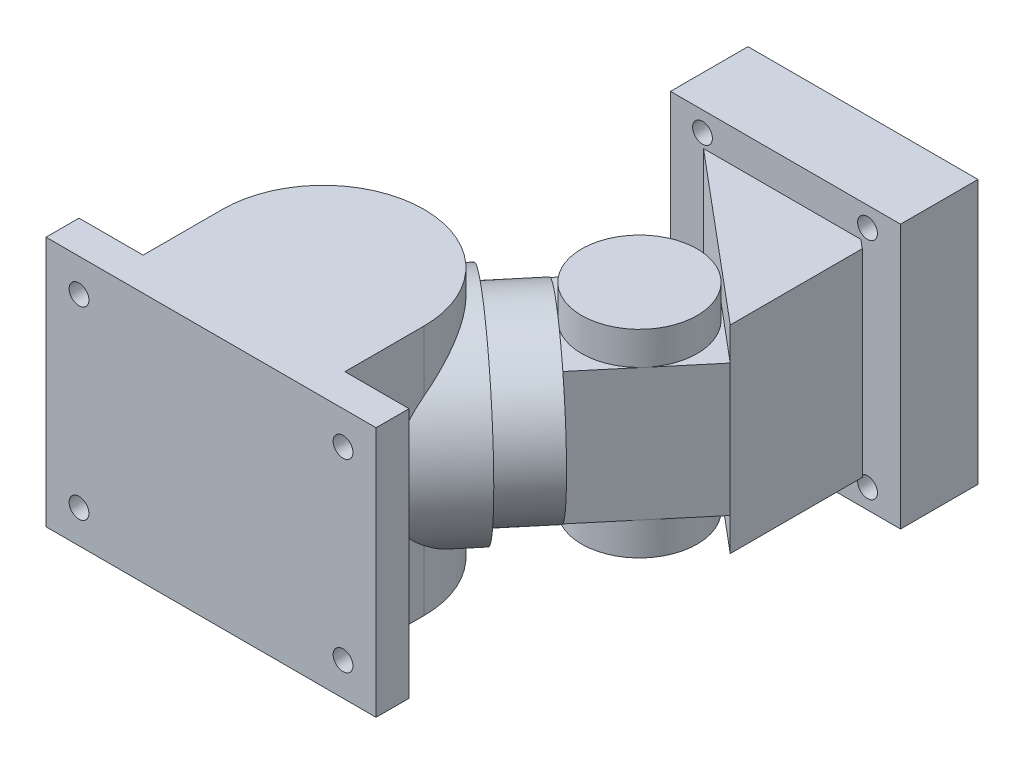
SolidWorks part; units mm, degrees
material "ABS"
ref_plane "Alzado" through (0, 0, 0) normal (0, 0, 1) x (1, 0, 0)
ref_plane "Planta" through (0, 0, 0) normal (0, 1, 0) x (1, 0, 0)
ref_plane "Vista lateral" through (0, 0, 0) normal (1, 0, 0) x (0, 0, -1)
sketch "Croquis1" plane through (0, 0, 0) normal (0, 1, 0) x (1, 0, 0)
  line L0 (0, 0) -> (0, 20)
  line L1 (0, 20) -> (-15.3209, 32.8558)
  line L2 (-15.3209, 32.8558) -> (-25.169, 21.1193)
  line L6 (0, 0) -> (-25.169, 21.1193)
  line L7 (0, 0) -> (-17.1631, 0) construction
  dimension "D1" = 20
  dimension "D2" = 20
  dimension "D5" = 130
extrude "Saliente-Extruir1" add sketch "Croquis1" along normal blind 15 and the other way blind 15
sketch "Croquis2" plane through (0, 0, 0) normal (0, 1, 0) x (1, 0, 0)
  line L0 (-13.4058, 11.2488) -> (0, 0)
  line L1 (-25.169, 21.1193) -> (0, 0) construction
  line L2 (0, 0) -> (-5.7851, -6.8944)
  line L4 (-19.1909, 4.3544) -> (-13.4058, 11.2488)
  circle A0 centre (-12.488, -1.27) radius 8.75
  point P4 (0, 0)
  point P5 (0, 0)
  point P10 (-26.0388, -3.8066)
  dimension "D1" = 17.5
  dimension "D2" = 90
  dimension "D3" = 90
  dimension "D4" = 9
extrude "Saliente-Extruir3" add sketch "Croquis2" along normal blind 10 and the other way blind 10 contours A0 | A0 L0 L4 | A0 L2 L0 region at (-6.7199, 0, -5.6042) region at (-12.488, 0, 1.27)
sketch "Croquis4" plane through (0, 10, 0) normal (0, 1, 0) x (1, 0, 0)
  circle A0 centre (-12.488, -1.27) radius 8.75
  arc A1 (-19.1909, 4.3544) -> (-5.7851, -6.8944) centre (-12.488, -1.27) ccw construction
extrude "Saliente-Extruir9" add sketch "Croquis4" along normal blind 5 and the other way blind 25
sketch "Croquis5" plane through (0, 0, 0) normal (0, 1, 0) x (1, 0, 0)
  line L0 (-93.3589, -57.8135) -> (-14.6565, -57.8135)
  line L2 (-19.1909, 4.3544) -> (-24.976, -2.54)
  line L3 (-24.976, -2.54) -> (-11.5702, -13.7888)
  line L4 (-5.7851, -6.8944) -> (-11.5702, -13.7888)
  circle A0 centre (-12.488, -1.27) radius 8.75
  circle A1 centre (-12.488, -1.27) radius 8.75 construction
  point P5 (-12.8716, -31.2066)
  point P6 (0, 0)
  point P7 (0, 0)
  point P12 (-24.976, -37.1418)
  point P13 (-11.9019, -23.9717)
  dimension "D1" = 9
  dimension "D2" = 90
  dimension "D4" = 50
extrude "Saliente-Extruir10" add sketch "Croquis5" along normal blind 10 and the other way blind 10 contours A0 | A0 L2 L3 L4 region at (-18.1293, 0, 7.9931) region at (-12.488, 0, 1.27)
sketch "Croquis6" plane through (-11.5702, 0, 13.7888) normal (-0.6428, 0, 0.766) x (0.766, 0, 0.6428)
  line L0 (0, -10) -> (0, 10) construction
  circle A0 centre (-8.75, 0) radius 13.2877
  point P2 (-24.1554, -1.349)
  point P3 (0, 0)
  point P10 (0, 0)
extrude "Saliente-Extruir11" add sketch "Croquis6" along normal blind 8
sketch "Croquis7" plane through (-16.7125, 0, 19.9172) normal (-0.6428, 0, 0.766) x (0.766, 0, 0.6428)
  circle A0 centre (-8.75, 0) radius 15.2877
  circle A1 centre (-8.75, 0) radius 13.2877 construction
  dimension "D1" = 2
extrude "Saliente-Extruir12" add sketch "Croquis7" along normal blind 17
sketch "Croquis9" plane through (0, 0, 0) normal (0, 1, 0) x (1, 0, 0)
  line L2 (-46.0538, -17.4888) -> (-22.6317, -37.1423) construction
  circle A0 centre (-34.3428, -27.3155) radius 15.2877
extrude "Saliente-Extruir13" add sketch "Croquis9" along normal blind 17 and the other way blind 17 contours A0 | A0 region at (-34.3428, 0, 27.3155)
sketch "Croquis10" plane through (0, 17, 0) normal (0, 1, 0) x (1, 0, 0)
  line L0 (-49.6304, -27.3155) -> (-49.6304, -39.3155)
  line L1 (-49.6304, -39.3155) -> (-59.3428, -39.3155)
  line L2 (-59.3428, -39.3155) -> (-59.3428, -44.3155)
  line L3 (-59.3428, -44.3155) -> (-9.3428, -44.3155)
  line L4 (-9.3428, -44.3155) -> (-9.3428, -39.3155)
  line L5 (-9.3428, -39.3155) -> (-19.0551, -39.3155)
  line L6 (-19.0551, -27.3155) -> (-19.0551, -39.3155)
  arc A0 (-19.0551, -27.3155) -> (-49.6304, -27.3155) centre (-34.3428, -27.3155) ccw
  arc A2 (-22.6317, -37.1423) -> (-46.0538, -17.4888) centre (-34.3428, -27.3155) ccw construction
  point P1 (-88.8925, -113.8582)
  point P8 (0, 0)
  point P10 (-36.2233, -128.8582)
  point P13 (-31.3925, -128.8582)
  point P14 (-88.8925, -117.1694)
  point P18 (-56.5011, -66.6791)
  point P19 (0, 0)
  dimension "D3" = 25
  dimension "D1" = 5
  dimension "D2" = 50
  dimension "D5" = 12
extrude "Saliente-Extruir14" add sketch "Croquis10" along normal blind 2 and the other way blind 36
sketch "Croquis11" plane through (0, 15, 0) normal (0, 1, 0) x (1, 0, 0)
  line L0 (-30.169, 21.1193) -> (4.6791, 21.1193)
  line L1 (4.6791, 21.1193) -> (4.6791, 32.8558)
  line L2 (4.6791, 32.8558) -> (-30.169, 32.8558)
  line L3 (-30.169, 32.8558) -> (-30.169, 21.1193)
  point P5 (-32.8294, 39.3878)
  point P6 (-49.4345, 27.6398)
  point P7 (0, 0)
  point P9 (-2.6686, 29.1809)
  point P12 (4.6791, 21.1193)
  point P13 (0, 0)
  point P14 (-30.169, 32.8558)
  point P15 (4.6791, 17.7769)
  point P16 (0, 0)
  dimension "D1" = 5
  dimension "D2" = 20
extrude "Saliente-Extruir15" add sketch "Croquis11" along normal blind 5 and the other way blind 35
sketch "Croquis12" plane through (0, 0, -21.1193) normal (0, 0, 1) x (1, 0, 0)
  line L0 (-30.169, 20) -> (4.6791, 20) construction
  line L1 (4.6791, -20) -> (4.6791, 20) construction
  circle A0 centre (-0.3209, 17) radius 1.5
  circle A1 centre (-25.3209, 17) radius 1.5
  circle A2 centre (-25.3209, -17) radius 1.5
  circle A3 centre (-0.3209, -17) radius 1.5
  point P8 (0, 0)
  point P9 (0, 0)
  point P18 (0, 0)
  point P19 (0, 0)
  point P20 (0, 0)
  dimension "D1" = 3
  dimension "D2" = 3
  dimension "D3" = 5
  dimension "D4" = 34
  dimension "D5" = 25
extrude "Cortar-Extruir1" cut sketch "Croquis12" against normal blind 35000
sketch "Croquis13" plane through (0, 0, 39.3155) normal (0, 0, -1) x (-1, 0, 0)
  line L0 (59.3428, -19) -> (59.3428, 19) construction
  line L1 (49.6304, 19) -> (59.3428, 19) construction
  line L2 (49.6304, -19) -> (59.3428, -19) construction
  line L3 (9.3428, -19) -> (9.3428, 19) construction
  circle A0 centre (54.3428, 14) radius 1.5
  circle A1 centre (54.3428, -14) radius 1.5
  circle A2 centre (14.3428, 14) radius 1.5
  circle A3 centre (14.3428, -14) radius 1.5
  point P8 (0, 0)
  point P9 (0, 0)
  point P10 (0, 0)
  point P11 (0, 0)
  dimension "D1" = 3
  dimension "D5" = 5
  dimension "D2" = 5
  dimension "D3" = 5
  dimension "D4" = 5
extrude "Cortar-Extruir2" cut sketch "Croquis13" against normal blind 35000
